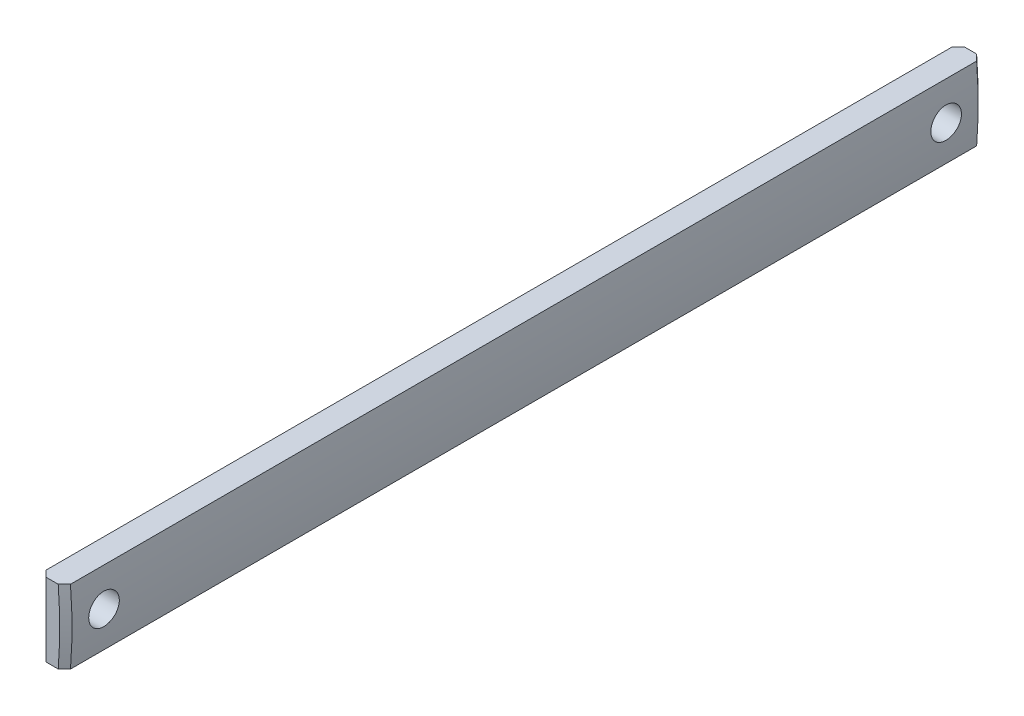
SolidWorks part; units mm, degrees
material "7075-T6, Piastra (SS)"
ref_plane "Piano frontale" through (0, 0, 0) normal (0, 0, 1) x (1, 0, 0)
ref_plane "Piano superiore" through (0, 0, 0) normal (0, 1, 0) x (1, 0, 0)
ref_plane "Piano destro" through (0, 0, 0) normal (1, 0, 0) x (0, 0, -1)
sketch "Schizzo1" plane through (0, 0, 0) normal (0, 0, 1) x (1, 0, 0)
  line L0 (68.753, 6) -> (68.753, -6)
  line L1 (68.753, -6) -> (72.753, -6)
  line L2 (68.753, 6) -> (72.753, 6)
  arc A0 (72.753, 6) -> (72.753, -6) centre (0, 0) cw
extrude "Estrusione-Estrusione1" add sketch "Schizzo1" along normal up to surface (150 mm away)
chamfer "Smusso1" distance 1 angle 45 4 edges at (68.753, 0, 150) (68.753, 0, 0) (73, 0, 150) (73, 0, 0)
sketch "Schizzo2" plane through (68.753, 0, 0) normal (-1, 0, 0) x (0, 0, 1)
  circle A0 centre (6.2292, 0) radius 2.5
extrude "Taglio-Estrusione1" cut sketch "Schizzo2" against normal through all separate body
ref_plane "Piano1" through (0, 0, 75) normal (0, 0, -1) x (-1, 0, 0)
mirror "Specchia1" about plane through (0, 0, 75) normal (0, 0, -1) of "Taglio-Estrusione1"
